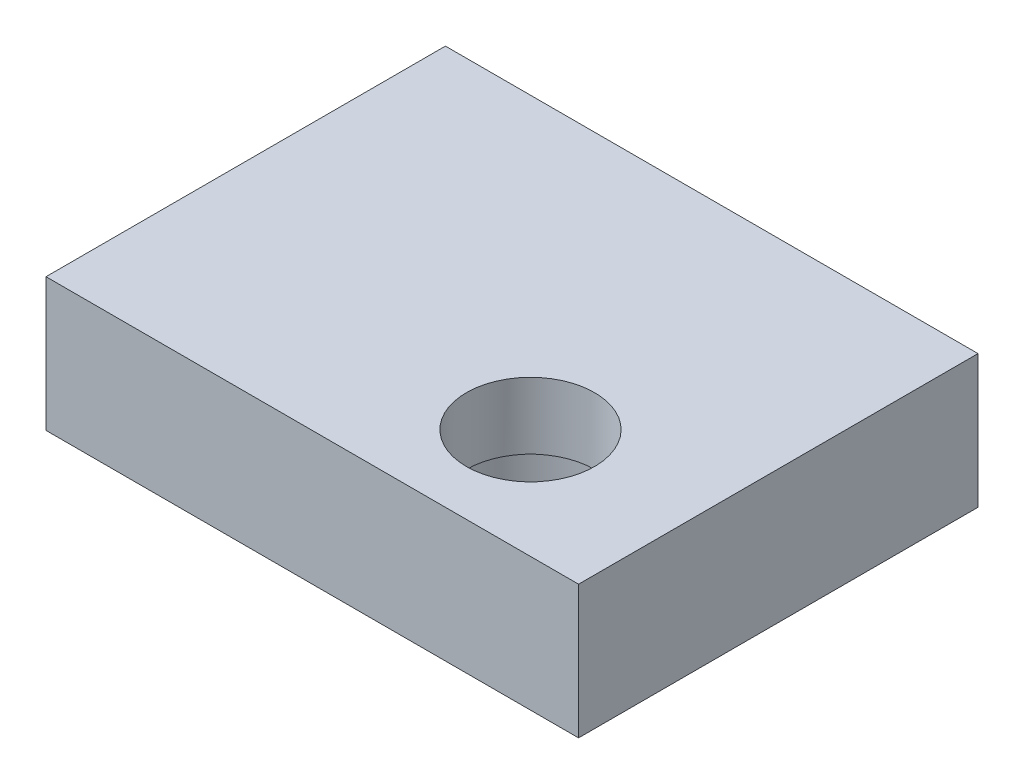
SolidWorks part; units mm, degrees
ref_plane "Front Plane" through (0, 0, 0) normal (0, 0, 1) x (1, 0, 0)
ref_plane "Top Plane" through (0, 0, 0) normal (0, 1, 0) x (1, 0, 0)
ref_plane "Right Plane" through (0, 0, 0) normal (1, 0, 0) x (0, 0, -1)
sketch "Sketch1" plane through (0, 0, 0) normal (0, 1, 0) x (1, 0, 0)
  line L1 (-20, -15) -> (20, -15)
  line L2 (-20, -15) -> (-20, 15)
  line L3 (-20, 15) -> (20, 15)
  line L4 (20, -15) -> (20, 15)
  line L5 (-20, -15) -> (20, 15) construction
  line L6 (-20, 15) -> (20, -15) construction
  point P0 (0, 0)
  dimension "D1" = 40
  dimension "D2" = 30
extrude "Boss-Extrude1" add sketch "Sketch1" along normal blind 10
sketch "Sketch2" plane through (0, 0, 0) normal (0, -1, 0) x (-1, 0, 0)
  line L0 (20, 0) -> (-20, 0) construction
  line L1 (20, 15) -> (20, -15) construction
  line L2 (-20, -15) -> (-20, 15) construction
  line L3 (-20, -15) -> (20, 15) construction
  line L4 (20, -15) -> (-20, 15) construction
  line L5 (0, -15) -> (0, 15) construction
  line L6 (20, -15) -> (-20, -15) construction
  line L7 (-20, 15) -> (20, 15) construction
  circle A0 centre (13.3333, -10) radius 2
  circle A1 centre (13.3333, 10) radius 2
  circle A2 centre (-13.3333, 10) radius 2
  circle A3 centre (-8.14, -6.75) radius 6.25
  dimension "D1" = 4
  dimension "D3" = 12.5
  dimension "D2" = 5
  dimension "D4" = 11.86
  dimension "D5" = 8.25
extrude "Cut-Extrude1" cut sketch "Sketch2" against normal blind 5
sketch "Sketch3" plane through (0, 10, 0) normal (0, 1, 0) x (1, 0, 0)
  line L0 (20, -15) -> (20, 15) construction
  line L1 (-20, -15) -> (20, -15) construction
  circle A0 centre (8.14, -6.75) radius 4.8125
  dimension "D1" = 9.625
  dimension "D2" = 11.86
  dimension "D3" = 8.25
extrude "Cut-Extrude2" cut sketch "Sketch3" against normal up to surface (10 mm away) up to face at (8.14, 0, 0.5)
